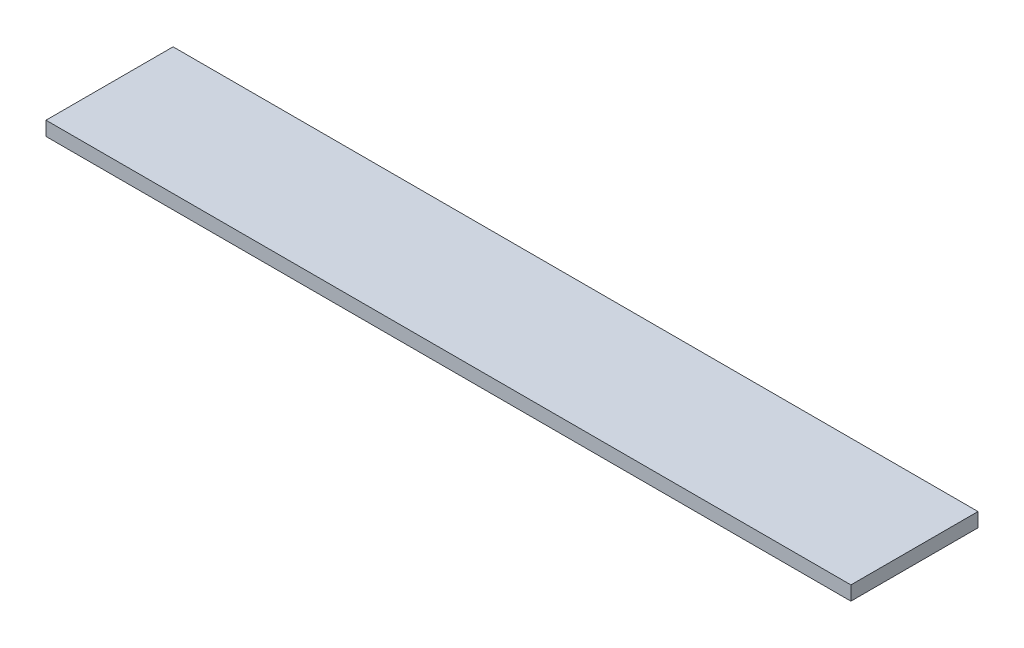
SolidWorks part; units mm, degrees
ref_plane "Front" through (0, 0, 0) normal (0, 0, 1) x (1, 0, 0)
ref_plane "Top" through (0, 0, 0) normal (0, 1, 0) x (1, 0, 0)
ref_plane "Right" through (0, 0, 0) normal (1, 0, 0) x (0, 0, -1)
sketch "Sketch1" plane through (0, 0, 0) normal (0, 1, 0) x (1, 0, 0)
  line L5 (0, 0) -> (228, 0)
  line L6 (0, 0) -> (0, 36)
  line L11 (0, 36) -> (228, 36)
  line L12 (228, 0) -> (228, 36)
  dimension "D1" = 36
  dimension "D2" = 228
extrude "Boss-Extrude2" add sketch "Sketch1" along normal blind 4
